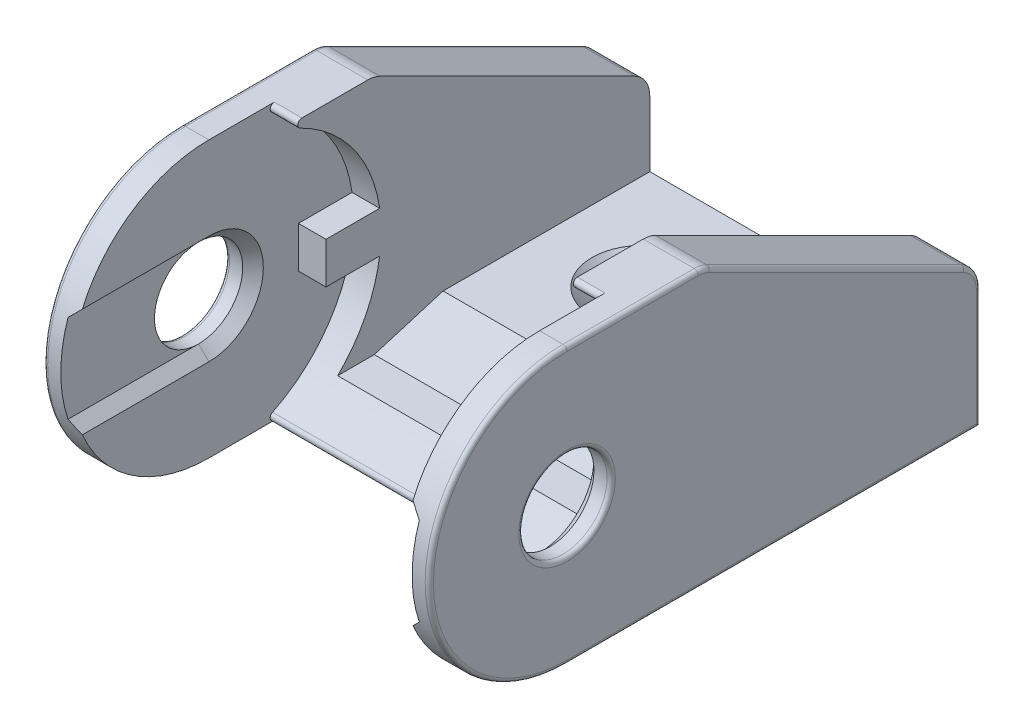
SolidWorks part; units mm, degrees
ref_plane "Front Plane" through (0, 0, 0) normal (0, 0, 1) x (1, 0, 0)
ref_plane "Top Plane" through (0, 0, 0) normal (0, 1, 0) x (1, 0, 0)
ref_plane "Right Plane" through (0, 0, 0) normal (1, 0, 0) x (0, 0, -1)
sketch "Sketch1" plane through (0, 0, 0) normal (1, 0, 0) x (0, 0, -1)
  line L1 (30, -10) -> (0, -10)
  line L2 (30, -10) -> (30, 10)
  line L3 (30, 10) -> (0, 10)
  line L4 (0, -10) -> (0, 10) construction
  arc A0 (0, 10) -> (0, -10) centre (0, 0) ccw
  dimension "D4" = 40
  dimension "D3" = 20
extrude "Boss-Extrude1" add sketch "Sketch1" along normal mid plane 28
sketch "Sketch2" plane through (14, 0, 0) normal (1, 0, 0) x (0, 0, -1)
  line L0 (30, 0) -> (10, 10)
  line L1 (30, -10) -> (30, 10) construction
  line L2 (30, 10) -> (0, 10) construction
  line L3 (10, 10) -> (30, 10)
  line L4 (30, 10) -> (30, 0)
  circle A0 centre (0, 0) radius 3.2
  dimension "D2" = 6.4
  dimension "D1" = 20
extrude "Cut-Extrude1" cut sketch "Sketch2" against normal blind 48
sketch "Sketch4" plane through (0, 0, 0) normal (1, 0, 0) x (0, 0, -1)
  line L16 (0, -10) -> (30, -10) construction
  line L17 (30, -10) -> (30, 0) construction
  line L18 (10, 10) -> (30, 0) construction
  line L19 (0, -10) -> (1.5, -10)
  line L20 (30, -6) -> (30, 0)
  line L21 (10, 10) -> (30, 0)
  line L26 (10, -7.5) -> (1.5, -7.5)
  line L27 (1.5, -7.5) -> (1.5, -10)
  line L28 (1.5, 7.5) -> (1.5, -7.5) construction
  line L29 (0, 10) -> (10, 10)
  line L30 (0, 10) -> (0, 7.5) construction
  line L31 (0, 7.5) -> (10, 7.5) construction
  line L32 (10, 7.5) -> (10, 10) construction
  line L33 (0, 0) -> (1.5, 0) construction
  line L34 (10, -7.5) -> (15, -6)
  line L35 (15, -6) -> (30, -6)
  arc A2 (0, 10) -> (0, -10) centre (0, 0) ccw construction
  arc A3 (0, 10) -> (0, -10) centre (0, 0) ccw
  dimension "D1" = 1.5
  dimension "D2" = 15
  dimension "D3" = 4
  dimension "D4" = 15
  dimension "D5" = 5
extrude "Cut-Extrude2" cut sketch "Sketch4" against normal mid plane 20
sketch "Sketch6" plane through (0, 0, 0) normal (1, 0, 0) x (0, 0, -1)
  line L0 (0, 0) -> (6.5, 0) construction
  line L1 (10.3923, 1.5) -> (6.5, 1.5)
  line L3 (10.3923, -1.5) -> (6.5, -1.5)
  line L4 (6.5, 1.5) -> (6.5, -1.5)
  line L5 (0, 0) -> (-10.5, 0) construction
  arc A0 (10.3923, 1.5) -> (10.3923, -1.5) centre (0, 0) ccw
  dimension "D1" = 21
  dimension "D2" = 3
  dimension "D3" = 17
extrude "Cut-Extrude4" cut sketch "Sketch6" against normal mid plane 24
fillet "Fillet1" radius 0.3 3 edges at (11, 10, -3.2016) (-11, 10, -3.2016) (0, -10, -3.2016)
sketch "Sketch5" plane through (0, -10, 0) normal (0, 1, 0) x (1, 0, 0)
  line L0 (-3, 22.5) -> (3, 22.5) construction
  line L1 (-3, 24.2) -> (3, 24.2)
  line L2 (-3, 20.8) -> (3, 20.8)
  line L3 (0, 22.5) -> (0, 0) construction
  line L5 (3, 22.5) -> (10, 22.5) construction
  line L6 (10, 15) -> (10, 30) construction
  arc A0 (-3, 24.2) -> (-3, 20.8) centre (-3, 22.5) ccw
  arc A1 (3, 20.8) -> (3, 24.2) centre (3, 22.5) ccw
  point P2 (0, 22.5)
  dimension "D1" = 3.4
  dimension "D2" = 6
extrude "Cut-Extrude3" cut sketch "Sketch5" along normal up to surface (4 mm away) up to face at (0, -6, -22.5)
chamfer "Chamfer1" distance 2 angle 45 4 edges at (0, -6, -24.2) (4.7, -6, -22.5) (-4.7, -6, -22.5) (0, -6, -20.8)
fillet "Fillet2" radius 2 4 edges at (-12, 0, -30) (12, 0, -30) (-12, 10, -10) (12, 10, -10)
fillet "Fillet3" radius 0.3 16 edges at (-14, 10, -4.7639) (-14, 0, 10) (-14, -10, -15) (-14, -5.618, -30) (-14, -0.1846, -29.7013) (-14, 5.1708, -19.6584) (-14, 0, -3.2) (14, 0, -3.2) (14, -10, -15) (14, 0, 10) (14, 10, -4.7639) (14, 5.1708, -19.6584) (14, -0.1846, -29.7013) (14, -5.618, -30) (-14, 9.9465, -9.9874) (14, 9.9465, -9.9874)
sketch "Sketch7" plane through (0, 0, 0) normal (0, 1, 0) x (1, 0, 0)
  line L0 (12, -10) -> (13.7, -10) construction
  line L1 (-12.75, 0) -> (12.75, 0)
  line L2 (-12.75, 0) -> (-12.75, -10)
  line L3 (-12.75, -10) -> (12.75, -10)
  line L4 (12.75, 0) -> (12.75, -10)
  point P6 (0, 0)
  point P7 (0, 0)
  point P9 (0, 0)
  dimension "D1" = 25.5
extrude "Cut-Extrude5" cut sketch "Sketch7" against normal mid plane 6.4
chamfer "Chamfer2" distance 0.75 angle 45 6 edges at (12, 3.2, 4.7371) (12, -3.2, 4.7371) (12, 0, -3.2) (-12, 3.2, 4.7371) (-12, -3.2, 4.7371) (-12, 0, -3.2)
